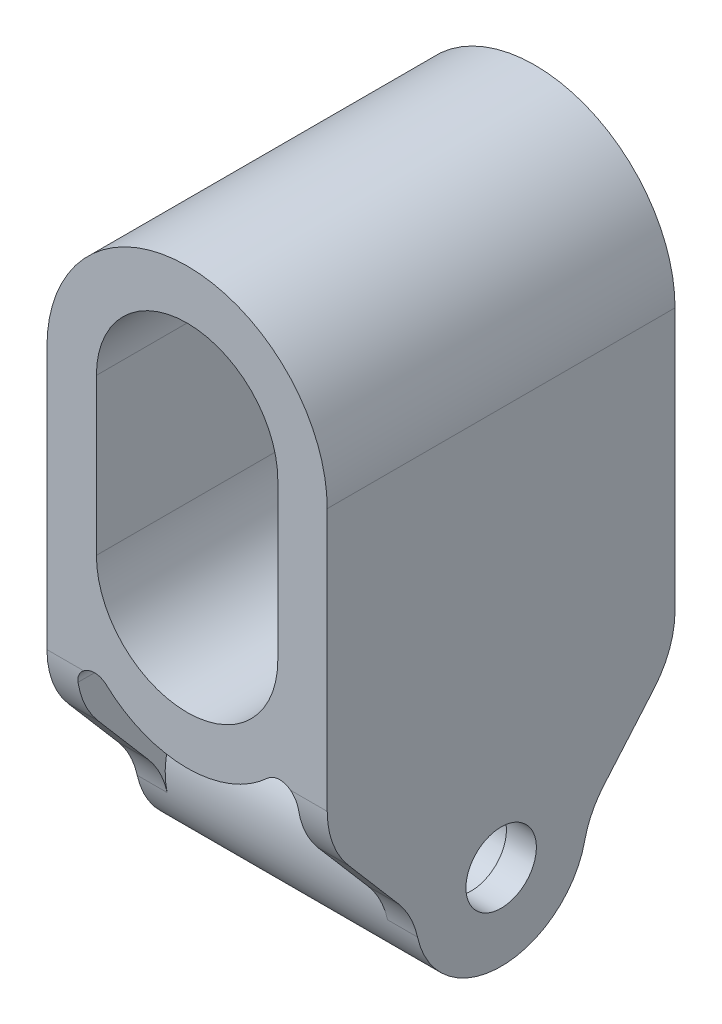
SolidWorks part; units mm, degrees
material "6061-T6 (SS)"
ref_plane "Front Plane" through (0, 0, 0) normal (0, 0, 1) x (1, 0, 0)
ref_plane "Top Plane" through (0, 0, 0) normal (0, 1, 0) x (1, 0, 0)
ref_plane "Right Plane" through (0, 0, 0) normal (1, 0, 0) x (0, 0, -1)
sketch "Sketch2" plane through (0, 0, 0) normal (0, 0, 1) x (1, 0, 0)
  line L1 (-15.915, 0) -> (-15.915, -54.905)
  line L2 (15.915, 0) -> (15.915, -54.905)
  line L5 (-15.915, -54.905) -> (-12.515, -54.905)
  line L6 (-12.515, -54.905) -> (-12.515, -25)
  line L7 (15.915, -54.905) -> (12.515, -54.905)
  line L8 (12.515, -54.905) -> (12.515, -25)
  line L9 (0, 15.915) -> (-15.915, 15.915) construction
  line L10 (0, 15.915) -> (15.915, 15.915) construction
  line L12 (0, 0) -> (0, -17.7) construction
  line L13 (10.3, 0) -> (10.3, -17.7)
  line L14 (-10.3, 0) -> (-10.3, -17.7)
  arc A2 (10.3, 0) -> (-10.3, 0) centre (0, 0) ccw
  arc A3 (15.915, 0) -> (-15.915, 0) centre (0, 0) ccw
  arc A4 (-10.3, -17.7) -> (10.3, -17.7) centre (0, -17.7) ccw
  arc A5 (12.515, -25) -> (-12.515, -25) centre (0, -20) cw
  point P5 (0, -28)
  point P6 (-15.915, -32.8417)
  point P8 (16.1448, -54.1731)
  point P10 (-12.515, -26.1041)
  point P17 (0, -8.85)
  point P24 (-15.3103, -54.5513)
  point P25 (0, 0)
  dimension "D1" = 10.3
  dimension "D6" = 8
  dimension "D7" = 20
  dimension "D3" = 70.82
  dimension "D4" = 3.4
  dimension "D5" = 3.4
  dimension "D2" = 25.03
  dimension "D8" = 25
extrude "Boss-Extrude1" add sketch "Sketch2" along normal blind 39.5
sketch "Sketch3" plane through (-15.915, 0, 0) normal (-1, 0, 0) x (0, 0, 1)
  line L0 (39.5, -25) -> (0, -25) construction
  line L1 (39.5, -25) -> (0, -25) construction
  line L2 (0, -25) -> (10.025, -45.18) construction
  line L3 (39.5, -54.905) -> (0, -54.905) construction
  line L6 (39.5, -25) -> (29.475, -45.18) construction
  line L7 (19.75, -25) -> (19.75, -45.18) construction
  line L9 (0, -25) -> (0, -33.4768) construction
  line L11 (39.5, -54.905) -> (0, -54.905)
  line L12 (0, -25) -> (0, -33.4768)
  line L13 (0, -33.4768) -> (10.025, -45.18)
  line L14 (39.5, -33.4768) -> (39.5, -25) construction
  line L15 (39.5, -33.4768) -> (39.5, -25)
  line L16 (39.5, -33.4768) -> (29.475, -45.18)
  line L17 (0, -33.4768) -> (0, -54.905)
  line L18 (17.2065, -28.7704) -> (22.2065, -28.7704)
  line L19 (17.2065, -28.7704) -> (17.2065, -35.7704)
  line L20 (17.2065, -35.7704) -> (22.2065, -35.7704)
  line L21 (22.2065, -28.7704) -> (22.2065, -35.7704)
  line L22 (17.2065, -28.7704) -> (22.2065, -35.7704) construction
  line L23 (17.2065, -35.7704) -> (22.2065, -28.7704) construction
  line L24 (39.5, -54.905) -> (0, -54.905)
  line L25 (39.5, -33.4768) -> (39.5, -54.905)
  circle A2 centre (19.75, -45.18) radius 4.4
  circle A3 centre (19.75, -45.18) radius 9.725
  circle A4 centre (19.75, -25.18) radius 4.4
  point P15 (19.75, -32.8978)
  point P20 (19.7065, -32.2704)
  line M7 (0, 0) -> (0, -54.905)
  line M8 (0, -54.905) -> (39.5, -54.905)
  line M9 (39.5, -54.905) -> (39.5, 0)
  dimension "D1" = 19.45
  dimension "D2" = 8.8
  dimension "D3" = 20
  dimension "D4" = 5
  dimension "D5" = 7
extrude "Cut-Extrude1" cut sketch "Sketch3" against normal through all contours A3 L13 M7 M8 | A3 L24 L16 M9 region at (-15.915, -47.4385, 34.2166) region at (-15.915, -47.4385, 5.2834)
hole_wizard "M7 Clearance Hole1" positions "Sketch4" profile "Sketch5" hole size "M7" standard "ANSI Metric" end condition through all
sketch "Sketch4" plane through (-15.915, 0, 0) normal (-1, 0, 0) x (0, 0, 1)
  point P0 (19.75, -45.18)
sketch "Sketch5" plane through (-15.915, -45.18, 19.75) normal (0, 1, 0) x (0, 0, 1)
  line L0 (0, 0) -> (0, 31.83)
  line L1 (0, 31.83) -> (4, 31.83)
  line L2 (4, 31.83) -> (4, 0)
  line L5 (4, 0) -> (0, 0)
  line L11 (0, -6.35) -> (0, 107.95) construction
  dimension "Thru Hole Dia." = 8
  dimension "Thru Hole Depth" = 31.83
fillet "Fillet1" radius 10 8 edges at (-14.215, -45.18, 29.475) (14.215, -45.18, 29.475) (14.215, -33.4768, 39.5) (-14.215, -33.4768, 39.5) (-14.215, -45.18, 10.025) (14.215, -45.18, 10.025) (14.215, -33.4768, 0) (-14.215, -33.4768, 0)
fillet "Fillet3" radius 2 2 edges at (12.515, -25, 19.75) (-12.515, -25, 19.75)
extrude "Boss-Extrude2" add sketch "Sketch3<3>" against normal up to surface (28.43 mm away) contours A3 A2 | A4 L19 L20 A3 L21 | L20 A3 region at (-15.915, -51.8637, 13.0663) region at (-15.915, -35.644, 19.75) region at (-15.915, -32.4431, 19.7014) up to face at (12.515, -41.18, 19.75)
sketch "Sketch3<3>" plane through (-15.915, 0, 0) normal (-1, 0, 0) x (0, 0, 1) same geometry as "Sketch3"
